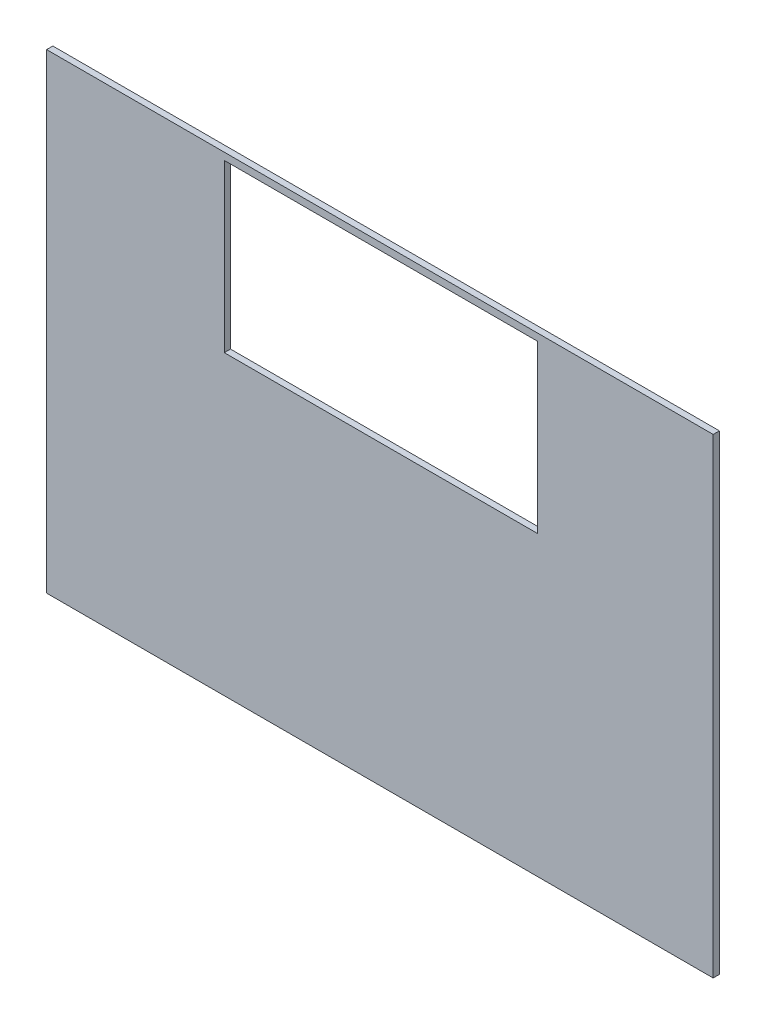
SolidWorks part; units mm, degrees
ref_plane "Front Plane" through (0, 0, 0) normal (0, 0, 1) x (1, 0, 0)
ref_plane "Top Plane" through (0, 0, 0) normal (0, 1, 0) x (1, 0, 0)
ref_plane "Right Plane" through (0, 0, 0) normal (1, 0, 0) x (0, 0, -1)
sketch "Sketch1" plane through (0, 0, 0) normal (0, 0, 1) x (1, 0, 0)
  line L1 (0, 0) -> (681.08, 0)
  line L2 (0, 0) -> (0, -481.0026)
  line L3 (0, -481.0026) -> (681.08, -481.0026)
  line L4 (681.08, 0) -> (681.08, -481.0026)
  dimension "D1" = 681.08
  dimension "D2" = 481.0026
extrude "Boss-Extrude1" add sketch "Sketch1" along normal blind 6.35
sketch "Sketch2" plane through (0, 0, 0) normal (0, 0, -1) x (-1, 0, 0)
  line L0 (-181.5418, -461.0026) -> (-181.5418, -13.0026) construction
  line L1 (-501.3881, -177.4089) -> (-181.5418, -177.4089)
  line L2 (-501.3881, -177.4089) -> (-501.3881, -7.2954)
  line L3 (-501.3881, -7.2954) -> (-181.5418, -7.2954)
  line L4 (-181.5418, -177.4089) -> (-181.5418, -7.2954)
  line L6 (-181.5418, -177.4089) -> (-501.7218, -177.4089) construction
  line L7 (-501.3881, -461.0026) -> (-501.3881, -13.0026) construction
extrude "Cut-Extrude1" cut sketch "Sketch2" against normal blind 10
